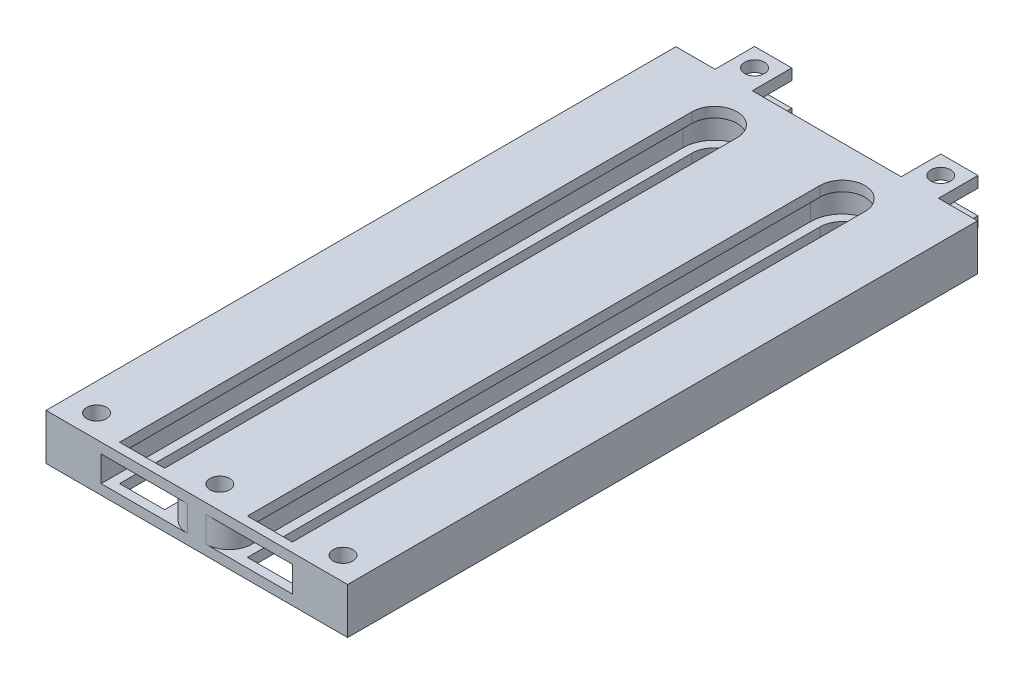
SolidWorks part; units mm, degrees
other "Markup1"
sketch "Sketch2" plane through (-32.8, 5, 137) normal (-0.1037, 0.0458, 0.9936) x (0.9781, 0.1859, 0.0936)
ref_plane "Front Plane" through (0, 0, 0) normal (0, 0, 1) x (1, 0, 0)
ref_plane "Top Plane" through (0, 0, 0) normal (0, 1, 0) x (1, 0, 0)
ref_plane "Right Plane" through (0, 0, 0) normal (1, 0, 0) x (0, 0, -1)
sketch "Sketch1" plane through (0, 0, 0) normal (0, 1, 0) x (1, 0, 0)
  line L0 (0, 0) -> (0, -137)
  line L1 (0, -137) -> (32.8, -137)
  line L2 (32.8, -137) -> (32.8, 0)
  line L3 (32.8, 0) -> (0, 0)
  line L4 (16.2, 0) -> (16.2, 8.6)
  line L5 (16.2, 8.6) -> (24.3, 8.6)
  line L6 (24.3, 8.6) -> (24.3, 0)
  line L7 (32.8, -2.5) -> (0, -2.5)
  line L8 (9, -10.5) -> (9, -135)
  line L9 (18.8, -10.5) -> (18.8, -135)
  line L10 (7, -135) -> (20.8, -135)
  line L11 (7, -10.5) -> (7, -135)
  line L12 (20.8, -10.5) -> (20.8, -135)
  line L13 (7, -135) -> (7, -137)
  line L14 (9, -135) -> (9, -137)
  line L15 (18.8, -135) -> (18.8, -137)
  line L16 (20.8, -135) -> (20.8, -137)
  circle A0 centre (20.25, 4.55) radius 2.15
  circle A1 centre (13.9, -10.5) radius 4.9
  circle A3 centre (13.9, -10.5) radius 6.9
  point P14 (20.25, 8.6)
  dimension "D1" = 20.25
  dimension "D4" = 4.3
  dimension "D6" = 2
  dimension "D7" = 13.8
  dimension "D2" = 32.8
  dimension "D3" = 8.1
  dimension "D5" = 137
  dimension "D8" = 7
  dimension "D9" = 2.5
  dimension "D10" = 10.5
  dimension "D11" = 2
  dimension "D12" = 8.6
  dimension "D13" = 4.55
extrude "Boss-Extrude1" add sketch "Sketch1" along normal blind 5 and the other way blind 5 contours A3 L12 L1 L2 L7 L0 L11 | A3 L11 L1 L8 | A3 L9 L1 L12 | L9 A3 L8 A1 | L7 L2 L3 L0 | L14 L10 L13 L1 | L15 L10 L14 L1 | L16 L10 L15 L1 region at (16.4, 0, 1.25) region at (16.4, 0, 3.8844) region at (8, 0, 136) region at (13.9, 0, 136) region at (7.9948, 0, 74.4177) region at (19.8, 0, 136) region at (13.9, 0, 3.7813) region at (19.8052, 0, 74.4177)
extrude "Cut-Extrude1" cut sketch "Sketch1<4>" against normal blind 2.8 and the other way blind 2.8 contours A3 L11 L10 L8 | A3 L9 L10 L12 | A3 L8 L10 L9 | L9 A3 L8 A1 | L8 A3 L9 A1 | A1 region at (7.9948, 0, 74.4177) region at (13.9, 0, 75.8813) region at (13.9, 0, 3.7813) region at (19.8052, 0, 74.4177) region at (9.1199, 0, 12.929) region at (13.9, 0, 10.5)
sketch "Sketch1<4>" plane through (0, 0, 0) normal (0, 1, 0) x (1, 0, 0) same geometry as "Sketch1"
extrude "Cut-Extrude3" cut sketch "Sketch1<8>" against normal blind 2.8 and the other way blind 2.8 contours L14 L10 L13 L1 | L16 L10 L15 L1 | L15 L10 L14 L1 region at (8, 0, 136) region at (13.9, 0, 136) region at (19.8, 0, 136)
sketch "Sketch1<8>" plane through (0, 0, 0) normal (0, 1, 0) x (1, 0, 0) same geometry as "Sketch1"
extrude "Boss-Extrude2" add sketch "Sketch1<5>" along normal up to surface (5 mm away) from offset 2.6 contours L6 L5 L4 L3 A0 region at (16.3181, 0, -4.3) up to face at (16.4, 5, 68.5)
sketch "Sketch1<5>" plane through (0, 0, 0) normal (0, 1, 0) x (1, 0, 0) same geometry as "Sketch1"
extrude "Boss-Extrude3" add sketch "Sketch1<6>" against normal up to surface (5 mm away) from offset 2.6 contours L6 L5 L4 L3 A0 region at (16.3181, 0, -4.3) up to face at (16.4, -5, 68.5) offset against normal yes
sketch "Sketch1<6>" plane through (0, 0, 0) normal (0, 1, 0) x (1, 0, 0) same geometry as "Sketch1"
mirror "Mirror1" about plane through (0, 0, 0) normal (1, 0, 0) of bodies 104
fillet "Fillet1" radius 5 2 edges at (-7, 0, 137) (7, 0, 137)
sketch "Sketch3" plane through (0, 0, 0) normal (0, 1, 0) x (1, 0, 0)
  line L0 (-32.8, -137) -> (32.8, -137) construction
  circle A0 centre (0, -132) radius 2.15
  circle A1 centre (26.8, -132) radius 2.15
  circle A2 centre (-26.8, -132) radius 2.15
  point P7 (0, 0)
  dimension "D1" = 4.3
  dimension "D2" = 5
  dimension "D3" = 26.8
  dimension "D4" = 26.8
extrude "Cut-Extrude4" cut sketch "Sketch3" against normal through all both and the other way through all
